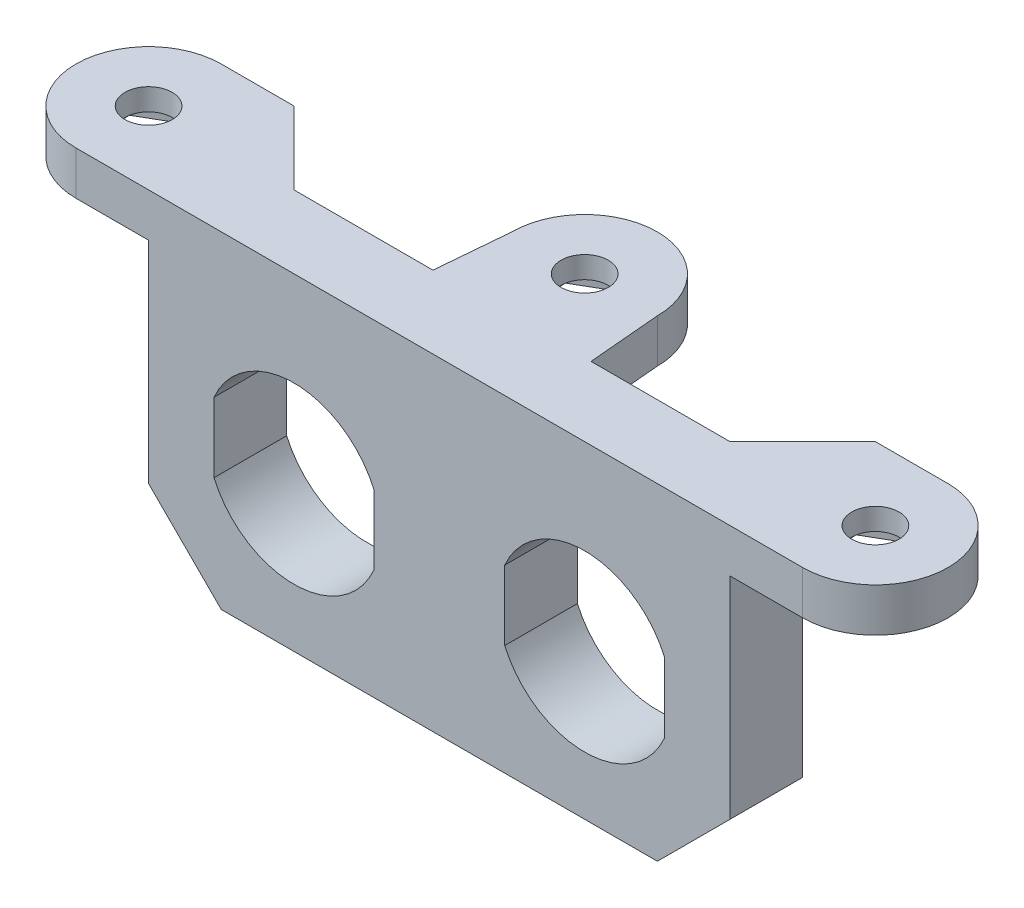
SolidWorks part; units mm, degrees
ref_plane "Front Plane" through (0, 0, 0) normal (0, 0, 1) x (1, 0, 0)
ref_plane "Top Plane" through (0, 0, 0) normal (0, 1, 0) x (1, 0, 0)
ref_plane "Right Plane" through (0, 0, 0) normal (1, 0, 0) x (0, 0, -1)
sketch "Sketch1" plane through (0, 0, 0) normal (0, 1, 0) x (1, 0, 0)
  line L0 (-25, 10) -> (-5, 10)
  line L1 (-25, 10) -> (25, 10) construction
  line L2 (-25, 10) -> (-25, 0) construction
  line L3 (-25, 0) -> (25, 0)
  line L4 (25, 10) -> (25, 0) construction
  line L5 (25, 10) -> (5, 10)
  arc A0 (-25, 10) -> (-25, 0) centre (-25, 5) ccw
  arc A1 (25, 0) -> (25, 10) centre (25, 5) ccw
  circle A2 centre (-25, 5) radius 1.625
  circle A3 centre (25, 5) radius 1.625
  arc A4 (5, 10) -> (-5, 10) centre (0, 10) ccw
  circle A5 centre (0, 10) radius 1.625
  point P4 (0, 0)
  dimension "D3" = 3.25
  dimension "D1" = 10
  dimension "D2" = 50
extrude "Boss-Extrude1" add sketch "Sketch1" along normal blind 22.5
sketch "Sketch5" plane through (0, 0, 0) normal (0, 1, 0) x (1, 0, 0)
  line L0 (0, 10) -> (0, 0) construction
  line L1 (-5, 10) -> (-20, 10)
  line L2 (-5, 10) -> (-5, 5)
  line L3 (-5, 5) -> (-20, 5)
  line L4 (-20, 10) -> (-20, 5)
  line L5 (-25, 0) -> (25, 0) construction
  line L6 (-25, 5) -> (25, 5) construction
  line L15 (20, 10) -> (20, 5)
  line L16 (5, 5) -> (20, 5)
  line L17 (5, 10) -> (5, 5)
  line L18 (5, 10) -> (20, 10)
  dimension "D1" = 5
  dimension "D2" = 5
extrude "Cut-Extrude1" cut sketch "Sketch5" along normal through all
sketch "Sketch6" plane through (0, 0, 0) normal (0, -1, 0) x (1, 0, 0)
  line L0 (-20, -10) -> (-25, -10) construction
  line L1 (0, 0) -> (0, -10) construction
  line L2 (-25, 0) -> (-20, 0)
  line L3 (-25, 0) -> (-25, -10) construction
  line L4 (-25, -10) -> (-20, -10)
  line L5 (-20, 0) -> (-20, -10)
  line L6 (25, 0) -> (25, -10) construction
  line L7 (20, 0) -> (20, -10)
  line L8 (25, -10) -> (20, -10)
  line L9 (25, 0) -> (20, 0)
  line L10 (5, -10) -> (5, -5) construction
  line L12 (-5, -5) -> (5, -5)
  line L13 (-5, -5) -> (-5, -10)
  line L14 (-5, -10) -> (5, -10) construction
  line L15 (5, -5) -> (5, -10)
  arc A0 (-25, 0) -> (-25, -10) centre (-25, -5) ccw
  arc A1 (25, 0) -> (25, -10) centre (25, -5) cw
  arc A2 (-5, -10) -> (5, -10) centre (0, -10) ccw
extrude "Cut-Extrude2" cut sketch "Sketch6" against normal blind 19.5
sketch "Sketch7" plane through (0, 0, -5) normal (0, 0, -1) x (-1, 0, 0)
  line L0 (0, 0) -> (0, 19.5) construction
  line L1 (20, 0) -> (-20, 0) construction
  line L2 (-5, 19.5) -> (5, 19.5) construction
  line L3 (-20, 19.5) -> (0, 19.5) construction
  line L4 (0, 19.5) -> (20, 19.5) construction
  line L5 (4.5, 12.3979) -> (4.5, 7.6021)
  line L6 (-15.5, 12.3979) -> (-4.5, 12.3979) construction
  line L7 (-15.5, 12.3979) -> (-15.5, 7.6021)
  line L8 (-15.5, 7.6021) -> (-4.5, 7.6021) construction
  line L9 (-4.5, 12.3979) -> (-4.5, 7.6021)
  line L10 (15.5, 12.3979) -> (15.5, 7.6021)
  arc A0 (-15.5, 7.6021) -> (-4.5, 7.6021) centre (-10, 10) ccw
  arc A1 (-4.5, 12.3979) -> (-15.5, 12.3979) centre (-10, 10) ccw
  arc A2 (4.5, 12.3979) -> (15.5, 12.3979) centre (10, 10) cw
  arc A3 (15.5, 7.6021) -> (4.5, 7.6021) centre (10, 10) cw
  point P18 (0, 0)
  point P19 (0, 0)
  point P20 (-10, 19.5)
  point P26 (0, 0)
  point P27 (-10, 9.3212)
  dimension "D1" = 12
  dimension "D2" = 11
  dimension "D3" = 10
extrude "Cut-Extrude3" cut sketch "Sketch7" against normal through all
chamfer "Chamfer1" distance 5 angle 45 2 edges at (-20, 21, -5) (20, 21, -5)
chamfer "Chamfer2" distance 5 angle 5 2 edges at (-5, 21, -5) (5, 21, -5) first distance on face at (-5, 21, -7.5) first distance on face at (5, 21, -7.5)
chamfer "Chamfer3" distance 5 angle 45 2 edges at (-20, 0, -2.5) (20, 0, -2.5)
sketch "Sketch8" plane through (0, 19.5, 0) normal (0, -1, 0) x (1, 0, 0)
  line L1 (25, -8.5796) -> (28.1, -6.7898)
  line L2 (28.1, -6.7898) -> (28.1, -3.2102)
  line L3 (28.1, -3.2102) -> (25, -1.4204)
  line L4 (25, -1.4204) -> (21.9, -3.2102)
  line L5 (21.9, -3.2102) -> (21.9, -6.7898)
  line L6 (21.9, -6.7898) -> (25, -8.5796)
  line L7 (0, -13.5796) -> (3.1, -11.7898)
  line L8 (3.1, -11.7898) -> (3.1, -8.2102)
  line L9 (3.1, -8.2102) -> (0, -6.4204)
  line L10 (0, -6.4204) -> (-3.1, -8.2102)
  line L11 (-3.1, -8.2102) -> (-3.1, -11.7898)
  line L12 (-3.1, -11.7898) -> (0, -13.5796)
  line L13 (-25, -8.5796) -> (-21.9, -6.7898)
  line L14 (-21.9, -6.7898) -> (-21.9, -3.2102)
  line L15 (-21.9, -3.2102) -> (-25, -1.4204)
  line L16 (-25, -1.4204) -> (-28.1, -3.2102)
  line L17 (-28.1, -3.2102) -> (-28.1, -6.7898)
  line L18 (-28.1, -6.7898) -> (-25, -8.5796)
  circle A0 centre (25, -5) radius 3.1 construction
  circle A1 centre (0, -10) radius 3.1 construction
  circle A2 centre (-25, -5) radius 3.1 construction
  dimension "D1" = 6.2
extrude "Cut-Extrude4" cut sketch "Sketch8" against normal blind 1.5
